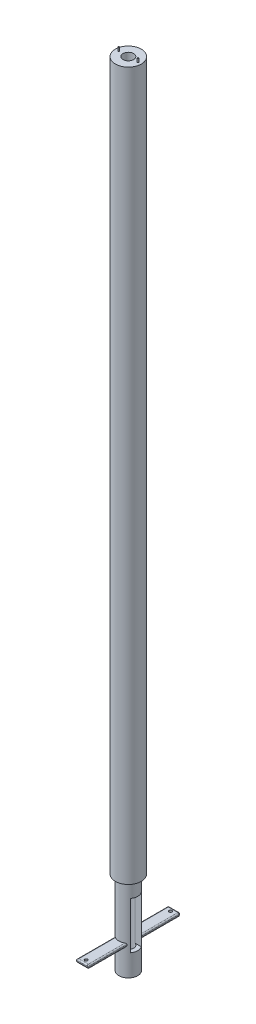
SolidWorks part; units mm, degrees
ref_plane "Front Plane" through (0, 0, 0) normal (0, 0, 1) x (1, 0, 0)
ref_plane "Top Plane" through (0, 0, 0) normal (0, 1, 0) x (1, 0, 0)
ref_plane "Right Plane" through (0, 0, 0) normal (1, 0, 0) x (0, 0, -1)
sketch "Sketch31" plane through (0, 0, 0) normal (0, 0, 1) x (1, 0, 0)
  line L0 (0, 0) -> (0, 35.4702)
sweep "Sweep3" add path "Sketch31" circular profile diameter 8 parameters "D3"=8
sketch "Sketch38" plane through (0, 0, 0) normal (0, 0, 1) x (1, 0, 0)
  line L1 (4, 35.4702) -> (-4, 35.4702) construction
  line L2 (0, 35.4702) -> (0, 336.2875)
sweep "Sweep4" add path "Sketch38" circular profile diameter 11 parameters "D3"=11
sketch "Sketch45" plane through (0, 0, 0) normal (0, 1, 0) x (1, 0, 0)
  circle A0 centre (0, 0) radius 2.25
extrude "Cut-Extrude2" cut sketch "Sketch45" along normal through all
sketch3d "3DSketch1"
  line L1 (0, 336.2875, 0) -> (0, 0, 0) construction
  line L2 (0, 336.2875, 0) -> (2.25, 336.2875, 0)
  line L18 (-5.5, 336.2875, 0) -> (-5.5, 336.2875, -5.5)
  line L19 (-5.5, 336.2875, -5.5) -> (0, 336.2875, -5.5)
  line L20 (0, 336.2875, -5.5) -> (5.5, 336.2875, -5.5)
  line L21 (5.5, 336.2875, -5.5) -> (5.5, 336.2875, 0)
  line L22 (0, 336.2875, 5.5) -> (5.5, 336.2875, 5.5)
  line L23 (5.5, 336.2875, 5.5) -> (5.5, 336.2875, 0)
  line L24 (0, 336.2875, 5.5) -> (-5.5, 336.2875, 5.5)
  line L25 (-5.5, 336.2875, 5.5) -> (-5.5, 336.2875, 0)
  circle A0 centre (0, 336.2875, 0) radius 2.25
  circle A1 centre (0, 336.2875, 0) radius 5.5 construction
  point P3 (0, 338.5375, 0)
  point P6 (0, 341.7875, 0)
  dimension "D1" = 5.5
  dimension "D3" = 5.5
  dimension "D2" = 5.5
  dimension "D4" = 5.5
  dimension "D5" = 5.5
  dimension "D6" = 5.5
  dimension "D7" = 5.5
  dimension "D8" = 5.5
sketch3d "3DSketch4"
  line L0 (4.125, 336.2875, 0) -> (4.125, 337.7875, 0)
  line L1 (-4.125, 336.2875, 0) -> (-4.125, 337.7875, 0)
  point P5 (-4.125, 336.2875, 0)
  point P6 (4.125, 336.2875, 0)
  dimension "D1" = 1.5
  dimension "D2" = 1.5
sweep "Sweep5" add path "3DSketch4" circular profile diameter 0.5 parameters "D3"=0.5
sketch3d "3DSketch5"
  line L0 (-4.125, 336.2875, 0) -> (-4.125, 337.7875, 0)
  line L1 (-5.5, 336.2875, 0) -> (-2.75, 336.2875, 0)
  line L2 (-4.125, 336.2875, 0) -> (-2.75, 336.2875, 0)
  dimension "D1" = 1.5
  dimension "D2" = 4.125
sweep "Sweep6" add path "3DSketch5" circular profile diameter 0.5 parameters "D3"=0.5
sketch "Sketch72" plane through (0, 0, 0) normal (1, 0, 0) x (0, 0, -1)
  line L0 (-2.318, 9.2361) -> (2.182, 9.2361)
  line L2 (-2.318, 9.2361) -> (-2.318, 29.2361)
  line L3 (-2.318, 29.2361) -> (2.182, 29.2361)
  line L4 (2.182, 29.2361) -> (2.182, 9.2361)
  dimension "D1" = 20
  dimension "D2" = 4.5
extrude "Cut-Extrude6" cut sketch "Sketch72" along normal blind 20
sketch "Sketch73" plane through (0, 0, 0) normal (0, 0, 1) x (1, 0, 0)
  line L0 (3.875, 337.7212) -> (4.3306, 337.589)
  line L1 (3.875, 337.7875) -> (3.875, 336.2875) construction
sketch "Sketch74" plane through (0, 0, 0) normal (0, 0, 1) x (1, 0, 0)
  point P5 (0, 12.0702)
sketch "Sketch76" plane through (0, 0, 0) normal (1, 0, 0) x (0, 0, -1)
  line L0 (3, 11.3702) -> (3, 12.7702)
  line L2 (-3, 12.0702) -> (-3, 12.7702)
  line L3 (3, 12.7702) -> (19.5, 12.7702)
  line L4 (-4, 35.4702) -> (4, 35.4702) construction
  line L5 (-3, 12.0702) -> (-3, 11.3702)
  line L6 (19.5, 11.3702) -> (19.5, 12.7702)
  line L7 (-19.5, 12.3702) -> (-19.5, 11.3702)
  line L8 (-19.5, 11.3702) -> (-3, 11.3702)
  line L9 (-19.5, 12.3702) -> (-19.5, 12.7702)
  line L10 (-19.5, 12.7702) -> (-3, 12.7702)
  line L12 (19.5, 11.3702) -> (3, 11.3702)
  line L14 (-3, 12.0702) -> (-3, 35.4702)
  dimension "D1" = 23.4
  dimension "D5" = 0.7
  dimension "D6" = 1.4
  dimension "D7" = 1.4
extrude "Boss-Extrude1" add sketch "Sketch76" along normal blind 2.5 and the other way blind 2.5 contours L10 L2 L5 L8 L7 L9
extrude "Boss-Extrude3" add sketch "Sketch76<4>" along normal blind 2.5 and the other way blind 2.5 contours L12 L6 L3 L0 region at (0, 12.0702, -11.25)
sketch "Sketch76<4>" plane through (0, 0, 0) normal (1, 0, 0) x (0, 0, -1) same geometry as "Sketch76"
sketch "Sketch77" plane through (0, 0, 0) normal (0, 1, 0) x (1, 0, 0)
  line L0 (-6.05, 0) -> (6.05, 0) construction
  circle A0 centre (0, 17.9) radius 0.6122
  circle A1 centre (0, -17.9) radius 0.6122
extrude "Cut-Extrude7" cut sketch "Sketch77" along normal blind 20
fillet "Fillet1" radius 0.5 14 edges at (-2.5, 12.7702, 11.3112) (-2.5, 11.3702, 11.3112) (2.5, 12.0702, 19.5) (0, 11.3702, 19.5) (2.5, 11.3702, 11.3112) (2.5, 12.7702, 11.3112) (0, 12.7702, 19.5) (-2.5, 11.3702, -11.3112) (-2.5, 12.7702, -11.3112) (0, 12.7702, -19.5) (0, 11.3702, -19.5) (2.5, 12.0702, -19.5) (2.5, 11.3702, -11.3112) (2.5, 12.7702, -11.3112)
sketch "Sketch81" plane through (0, 0, 0) normal (0, 0, 1) x (1, 0, 0)
  line L9 (-3.3708, 247.1784) -> (-51.6016, 269.074)
  line L10 (-51.6016, 269.074) -> (-3.592, 269.074)
  line L11 (-3.592, 269.074) -> (-3.592, 274.074)
  line L12 (-3.592, 274.074) -> (-49.3271, 274.074)
  line L13 (-49.3271, 274.074) -> (-55.2475, 261.3875)
  line L14 (-55.2475, 261.3875) -> (-3.3708, 237.1784)
  line L15 (-3.3708, 237.1784) -> (-3.3708, 247.1784)
  dimension "D1" = 5
  dimension "D2" = 10
  dimension "D3" = 14
  dimension "D4" = 45.7351
  dimension "D5" = 51.8767
  dimension "D6" = 57.2474
  dimension "D7" = 48.0096
  dimension "D8" = 52.9682
  dimension "D9" = 244.983
  dimension "D10" = 24.417
  dimension "D11" = 52.9682
extrude "Cut-Extrude9" cut sketch "Sketch81" against normal blind 3 and the other way blind 3 contours L10 L11 L12 L13 L14 L15 L9
